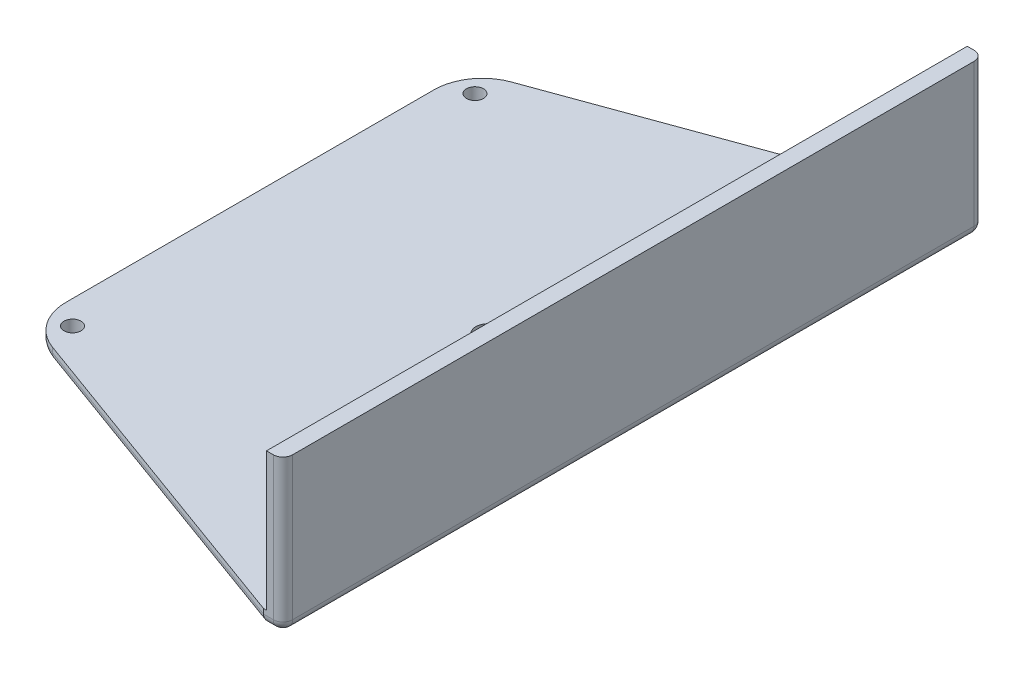
SolidWorks part; units mm, degrees
material "ABS"
ref_plane "Front Plane" through (0, 0, 0) normal (0, 0, 1) x (1, 0, 0)
ref_plane "Top Plane" through (0, 0, 0) normal (0, 1, 0) x (1, 0, 0)
ref_plane "Right Plane" through (0, 0, 0) normal (1, 0, 0) x (0, 0, -1)
sketch "Sketch1" plane through (0, 0, 0) normal (0, 1, 0) x (1, 0, 0)
  line L0 (-79.176, 45) -> (-79.176, -45)
  line L1 (-79.176, -45) -> (-4, -72.36)
  line L2 (-4, -72.36) -> (0, -72.36)
  line L3 (0, -72.36) -> (0, 72.36)
  line L4 (-79.176, 0) -> (0, 0) construction
  line L5 (-4, 72.36) -> (0, 72.36)
  line L6 (-79.176, 45) -> (-4, 72.36)
  dimension "D1" = 80
  dimension "D2" = 4
  dimension "D3" = 90
  dimension "D4" = 144.72
extrude "Boss-Extrude1" add sketch "Sketch1" along normal blind 3
sketch "Sketch2" plane through (0, 0, 0) normal (0, -1, 0) x (1, 0, 0)
  line L0 (-3.4, -72.36) -> (-3.4, 72.36)
  line L1 (0, -72.36) -> (-4, -72.36) construction
  line L2 (-4, 72.36) -> (0, 72.36) construction
  line L3 (0, 72.36) -> (0, -72.36) construction
  line L4 (-3.4, -72.36) -> (0, -72.36)
  line L5 (0, -72.36) -> (0, 72.36)
  line L6 (0, 72.36) -> (-3.4, 72.36)
  dimension "D1" = 3.4
extrude "Boss-Extrude2" add sketch "Sketch2" against normal blind 31.5
sketch "Sketch3" plane through (0, 3, 0) normal (0, 1, 0) x (1, 0, 0)
  line L0 (-79.176, -45) -> (-47.4658, -22.7963) construction
  line L4 (-79.176, 45) -> (-79.176, -45) construction
  line L5 (0, 0) -> (-79.176, 0) construction
  line L6 (0, -72.36) -> (0, 72.36) construction
  line L7 (-79.176, 45) -> (-47.4658, 22.7963) construction
  circle A0 centre (-74.2611, -41.5585) radius 1.75
  circle A1 centre (-74.2611, 41.5585) radius 1.75
  dimension "D2" = 3.5
  dimension "D1" = 55
  dimension "D3" = 6
extrude "Cut-Extrude1" cut sketch "Sketch3" against normal blind 40
fillet "Fillet1" radius 2 6 edges at (-79.176, 0, 0) (-41.588, 0, 58.68) (-2, 0, 72.36) (0, 0, 0) (-2, 0, -72.36) (-41.588, 0, -58.68)
fillet "Fillet2" radius 2 4 edges at (-0.5858, 0.5858, 71.7742) (-0.5858, 0.5858, -71.7742) (0, 16.75, 72.36) (0, 16.75, -72.36)
fillet "Congé1" radius 10 4 edges at (-78.5902, 0.5858, -44.5898) (-78.5902, 0.5858, 44.5898) (-79.176, 2.5, 45) (-79.176, 2.5, -45)
sketch "Esquisse2" plane through (0, 0, 0) normal (0, -1, 0) x (1, 0, 0)
  line L0 (0, 0) -> (-77.176, 0) construction
  line L1 (-10.25, 7.5) -> (-19.75, 7.5)
  line L2 (-10.25, 7.5) -> (-10.25, -7.5)
  line L3 (-10.25, -7.5) -> (-19.75, -7.5)
  line L4 (-19.75, 7.5) -> (-19.75, -7.5)
  line L5 (-10.25, 7.5) -> (-19.75, -7.5) construction
  line L6 (-10.25, -7.5) -> (-19.75, 7.5) construction
  line L7 (-77.176, 37.9978) -> (-77.176, -37.9978) construction
  circle A0 centre (-30, 0) radius 2.5
  point P0 (-15, 0)
  dimension "D1" = 5
  dimension "D2" = 30
  dimension "D3" = 9.5
  dimension "D4" = 15
  dimension "D5" = 15
extrude "Enlèv. mat.-Extru.1" cut sketch "Esquisse2" against normal blind 10
